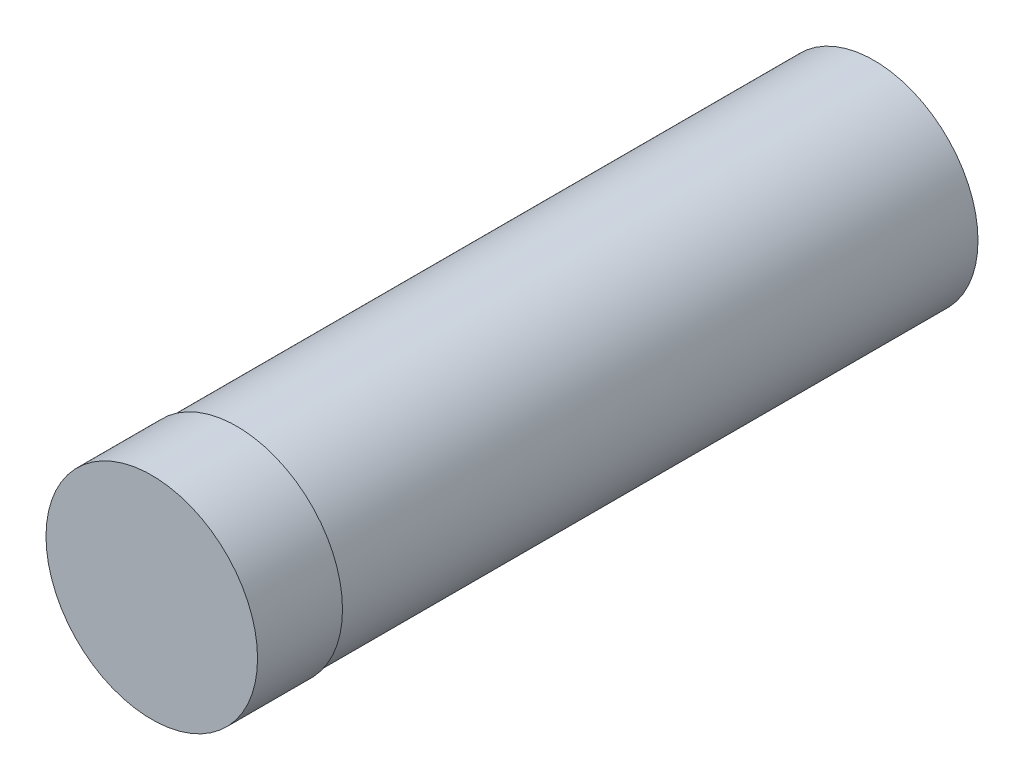
SolidWorks part; units mm, degrees
ref_plane "Front Plane" through (0, 0, 0) normal (0, 0, 1) x (1, 0, 0)
ref_plane "Top Plane" through (0, 0, 0) normal (0, 1, 0) x (1, 0, 0)
ref_plane "Right Plane" through (0, 0, 0) normal (1, 0, 0) x (0, 0, -1)
sketch "Sketch1" plane through (0, 0, 0) normal (0, 0, 1) x (1, 0, 0)
  circle A0 centre (0, 0) radius 2.45
  dimension "D1" = 4.9
extrude "Boss-Extrude1" add sketch "Sketch1" along normal mid plane 17
sketch "Sketch2" plane through (0, 0, 0) normal (0, 0, 1) x (1, 0, 0)
  circle A0 centre (0, 0) radius 2.5 construction
  dimension "D1" = 5
sketch "Sketch3" plane through (0, 0, 8.5) normal (0, 0, 1) x (1, 0, 0)
  circle A0 centre (0, 0) radius 2.49
  dimension "D1" = 4.98
extrude "Boss-Extrude2" add sketch "Sketch3" against normal blind 2
